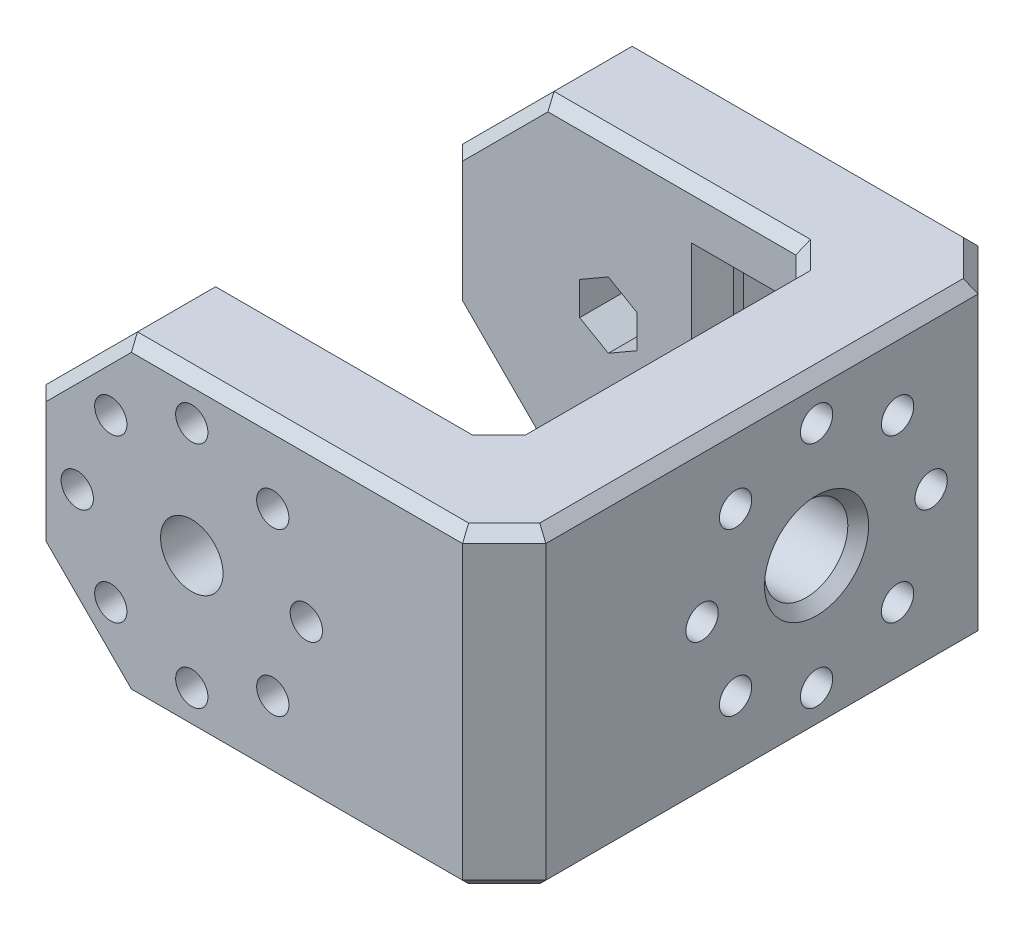
SolidWorks part; units mm, degrees
ref_plane "Alzado" through (0, 0, 0) normal (0, 0, 1) x (1, 0, 0)
ref_plane "Planta" through (0, 0, 0) normal (0, 1, 0) x (1, 0, 0)
ref_plane "Vista lateral" through (0, 0, 0) normal (1, 0, 0) x (0, 0, -1)
sketch "Croquis1" plane through (0, 0, 0) normal (0, 0, 1) x (1, 0, 0)
  line L0 (6.2132, 15) -> (30, 15)
  line L1 (15, -6.2132) -> (15, 6.2132) construction
  line L2 (15, 6.2132) -> (6.2132, 15) construction
  line L3 (6.2132, 15) -> (-6.2132, 15)
  line L4 (-6.2132, 15) -> (-15, 6.2132)
  line L5 (-15, 6.2132) -> (-15, -6.2132)
  line L6 (-15, -6.2132) -> (-6.2132, -15)
  line L7 (-6.2132, -15) -> (6.2132, -15)
  line L8 (6.2132, -15) -> (15, -6.2132) construction
  line L9 (30, 15) -> (30, -15)
  line L10 (30, -15) -> (6.2132, -15)
  circle A0 centre (0, 0) radius 15 construction
  dimension "D1" = 30
  dimension "D2" = 15
extrude "Saliente-Extruir1" add sketch "Croquis1" along normal blind 60
sketch "Croquis2" plane through (0, 15, 0) normal (0, 1, 0) x (1, 0, 0)
  line L0 (-15, -60) -> (-15, 0) construction
  line L1 (-15, -50.5) -> (20, -50.5)
  line L2 (-15, -50.5) -> (-15, -20)
  line L3 (-15, -20) -> (20, -20)
  line L4 (20, -50.5) -> (20, -20)
  line L5 (30, 0) -> (-6.2132, 0) construction
  line L6 (-15, -10.5) -> (20, -10.5)
  line L7 (-15, -10.5) -> (-15, 0)
  line L8 (-15, 0) -> (20, 0)
  line L9 (20, -10.5) -> (20, 0)
  line L10 (30, -60) -> (-6.2132, -60) construction
  line L11 (30, -60) -> (30, 0) construction
  dimension "D1" = 9.5
  dimension "D2" = 30.5
  dimension "D3" = 9.5
  dimension "D4" = 10
extrude "Cortar-Extruir1" cut sketch "Croquis2" against normal through all
sketch "Croquis3" plane through (0, 0, 60) normal (0, 0, 1) x (1, 0, 0)
  circle A0 centre (0, 0) radius 3
  dimension "D1" = 6
extrude "Cortar-Extruir2" cut sketch "Croquis3" against normal up to next
sketch "Croquis12" plane through (0, 0, 10.5) normal (0, 0, -1) x (-1, 0, 0)
  circle A0 centre (0, 0) radius 6
  dimension "D1" = 12
extrude "Saliente-Extruir2" add sketch "Croquis12" along normal blind 1
sketch "Croquis4" plane through (0, 0, 9.5) normal (0, 0, -1) x (-1, 0, 0)
  circle A0 centre (0, 0) radius 1.5
  dimension "D1" = 3
extrude "Cortar-Extruir3" cut sketch "Croquis4" against normal up to next
sketch "Croquis5" plane through (0, 0, 20) normal (0, 0, 1) x (1, 0, 0)
  line L1 (0, 3.1754) -> (-2.75, 1.5877)
  line L2 (-2.75, 1.5877) -> (-2.75, -1.5877)
  line L3 (-2.75, -1.5877) -> (0, -3.1754)
  line L4 (0, -3.1754) -> (2.75, -1.5877)
  line L5 (2.75, -1.5877) -> (2.75, 1.5877)
  line L6 (2.75, 1.5877) -> (0, 3.1754)
  circle A0 centre (0, 0) radius 2.75 construction
  dimension "D1" = 5.5
extrude "Cortar-Extruir4" cut sketch "Croquis5" against normal blind 5
sketch "Croquis9" plane through (0, 0, 20) normal (0, 0, 1) x (1, 0, 0)
  line L0 (20, -15) -> (20, 15) construction
  line L1 (20, -10) -> (10, -10)
  line L2 (20, -10) -> (20, 10)
  line L3 (20, 10) -> (10, 10)
  line L4 (10, -10) -> (10, 10)
  line L5 (-6.2132, -15) -> (30, -15) construction
  line L6 (30, 15) -> (-6.2132, 15) construction
  dimension "D1" = 5
  dimension "D2" = 5
  dimension "D3" = 10
extrude "Cortar-Extruir7" cut sketch "Croquis9" against normal blind 5
sketch "Croquis7" plane through (30, 0, 0) normal (1, 0, 0) x (0, 0, -1)
  line L0 (-60, 0) -> (0, 0) construction
  line L1 (-60, -15) -> (-60, 15) construction
  line L2 (-30, 15) -> (-30, -15) construction
  line L3 (-60, 15) -> (0, 15) construction
  line L4 (-60, -15) -> (0, -15) construction
  circle A0 centre (-30, 0) radius 4
  circle A1 centre (-30, 11) radius 1.55
  circle A2 centre (-22.2218, 7.7782) radius 1.55
  circle A3 centre (-19, 0) radius 1.55
  circle A4 centre (-22.2218, -7.7782) radius 1.55
  circle A5 centre (-30, -11) radius 1.55
  circle A6 centre (-37.7782, -7.7782) radius 1.55
  circle A7 centre (-41, 0) radius 1.55
  circle A8 centre (-37.7782, 7.7782) radius 1.55
  point P31 (-30, 0)
  dimension "D1" = 3.1
  dimension "D2" = 8
  dimension "D4" = 11
  dimension "D3" = 8
extrude "Cortar-Extruir5" cut sketch "Croquis7" against normal up to next
sketch "Croquis8" plane through (30, 0, 0) normal (1, 0, 0) x (0, 0, -1)
  line L0 (-19.9765, 5.5328) -> (-19.1546, 8.6)
  line L1 (-26.8246, 11) -> (-28.4123, 13.75)
  line L2 (-28.4123, 13.75) -> (-31.5877, 13.75)
  line L3 (-31.5877, 13.75) -> (-33.1754, 11)
  line L4 (-33.1754, 11) -> (-31.5877, 8.25)
  line L5 (-31.5877, 8.25) -> (-28.4123, 8.25)
  line L6 (-28.4123, 8.25) -> (-26.8246, 11)
  line L7 (-19.1546, 8.6) -> (-21.4, 10.8454)
  line L8 (-21.4, 10.8454) -> (-24.4672, 10.0235)
  line L9 (-24.4672, 10.0235) -> (-25.2891, 6.9563)
  line L10 (-25.2891, 6.9563) -> (-23.0437, 4.7109)
  line L11 (-23.0437, 4.7109) -> (-19.9765, 5.5328)
  line L12 (-19, -3.1754) -> (-16.25, -1.5877)
  line L13 (-16.25, -1.5877) -> (-16.25, 1.5877)
  line L14 (-16.25, 1.5877) -> (-19, 3.1754)
  line L15 (-19, 3.1754) -> (-21.75, 1.5877)
  line L16 (-21.75, 1.5877) -> (-21.75, -1.5877)
  line L17 (-21.75, -1.5877) -> (-19, -3.1754)
  line L18 (-24.4672, -10.0235) -> (-21.4, -10.8454)
  line L19 (-21.4, -10.8454) -> (-19.1546, -8.6)
  line L20 (-19.1546, -8.6) -> (-19.9765, -5.5328)
  line L21 (-19.9765, -5.5328) -> (-23.0437, -4.7109)
  line L22 (-23.0437, -4.7109) -> (-25.2891, -6.9563)
  line L23 (-25.2891, -6.9563) -> (-24.4672, -10.0235)
  line L24 (-33.1754, -11) -> (-31.5877, -13.75)
  line L25 (-31.5877, -13.75) -> (-28.4123, -13.75)
  line L26 (-28.4123, -13.75) -> (-26.8246, -11)
  line L27 (-26.8246, -11) -> (-28.4123, -8.25)
  line L28 (-28.4123, -8.25) -> (-31.5877, -8.25)
  line L29 (-31.5877, -8.25) -> (-33.1754, -11)
  line L30 (-40.0235, -5.5328) -> (-40.8454, -8.6)
  line L31 (-40.8454, -8.6) -> (-38.6, -10.8454)
  line L32 (-38.6, -10.8454) -> (-35.5328, -10.0235)
  line L33 (-35.5328, -10.0235) -> (-34.7109, -6.9563)
  line L34 (-34.7109, -6.9563) -> (-36.9563, -4.7109)
  line L35 (-36.9563, -4.7109) -> (-40.0235, -5.5328)
  line L36 (-41, 3.1754) -> (-43.75, 1.5877)
  line L37 (-43.75, 1.5877) -> (-43.75, -1.5877)
  line L38 (-43.75, -1.5877) -> (-41, -3.1754)
  line L39 (-41, -3.1754) -> (-38.25, -1.5877)
  line L40 (-38.25, -1.5877) -> (-38.25, 1.5877)
  line L41 (-38.25, 1.5877) -> (-41, 3.1754)
  line L42 (-35.5328, 10.0235) -> (-38.6, 10.8454)
  line L43 (-38.6, 10.8454) -> (-40.8454, 8.6)
  line L44 (-40.8454, 8.6) -> (-40.0235, 5.5328)
  line L45 (-40.0235, 5.5328) -> (-36.9563, 4.7109)
  line L46 (-36.9563, 4.7109) -> (-34.7109, 6.9563)
  line L47 (-34.7109, 6.9563) -> (-35.5328, 10.0235)
  circle A0 centre (-30, 11) radius 2.75 construction
  point P54 (-30, 0)
  dimension "D1" = 5.5
  dimension "D2" = 8
extrude "Cortar-Extruir6" cut sketch "Croquis8" against normal up to next from offset 5 offset against normal yes
sketch "Croquis10" plane through (0, 0, 60) normal (0, 0, 1) x (1, 0, 0)
  circle A0 centre (0, 11) radius 1.55
  circle A1 centre (0, 0) radius 3 construction
  circle A2 centre (7.7782, 7.7782) radius 1.55
  circle A3 centre (11, 0) radius 1.55
  circle A4 centre (7.7782, -7.7782) radius 1.55
  circle A5 centre (0, -11) radius 1.55
  circle A6 centre (-7.7782, -7.7782) radius 1.55
  circle A7 centre (-11, 0) radius 1.55
  circle A8 centre (-7.7782, 7.7782) radius 1.55
  point P21 (0, 0)
  dimension "D1" = 3.1
  dimension "D2" = 11
  dimension "D3" = 8
extrude "Cortar-Extruir8" cut sketch "Croquis10" against normal up to next
sketch "Croquis11" plane through (0, 0, 60) normal (0, 0, 1) x (1, 0, 0)
  line L0 (10.0235, 5.5328) -> (10.8454, 8.6)
  line L1 (3.1754, 11) -> (1.5877, 13.75)
  line L2 (1.5877, 13.75) -> (-1.5877, 13.75)
  line L3 (-1.5877, 13.75) -> (-3.1754, 11)
  line L4 (-3.1754, 11) -> (-1.5877, 8.25)
  line L5 (-1.5877, 8.25) -> (1.5877, 8.25)
  line L6 (1.5877, 8.25) -> (3.1754, 11)
  line L7 (10.8454, 8.6) -> (8.6, 10.8454)
  line L8 (8.6, 10.8454) -> (5.5328, 10.0235)
  line L9 (5.5328, 10.0235) -> (4.7109, 6.9563)
  line L10 (4.7109, 6.9563) -> (6.9563, 4.7109)
  line L11 (6.9563, 4.7109) -> (10.0235, 5.5328)
  line L12 (11, -3.1754) -> (13.75, -1.5877)
  line L13 (13.75, -1.5877) -> (13.75, 1.5877)
  line L14 (13.75, 1.5877) -> (11, 3.1754)
  line L15 (11, 3.1754) -> (8.25, 1.5877)
  line L16 (8.25, 1.5877) -> (8.25, -1.5877)
  line L17 (8.25, -1.5877) -> (11, -3.1754)
  line L18 (5.5328, -10.0235) -> (8.6, -10.8454)
  line L19 (8.6, -10.8454) -> (10.8454, -8.6)
  line L20 (10.8454, -8.6) -> (10.0235, -5.5328)
  line L21 (10.0235, -5.5328) -> (6.9563, -4.7109)
  line L22 (6.9563, -4.7109) -> (4.7109, -6.9563)
  line L23 (4.7109, -6.9563) -> (5.5328, -10.0235)
  line L24 (-3.1754, -11) -> (-1.5877, -13.75)
  line L25 (-1.5877, -13.75) -> (1.5877, -13.75)
  line L26 (1.5877, -13.75) -> (3.1754, -11)
  line L27 (3.1754, -11) -> (1.5877, -8.25)
  line L28 (1.5877, -8.25) -> (-1.5877, -8.25)
  line L29 (-1.5877, -8.25) -> (-3.1754, -11)
  line L30 (-10.0235, -5.5328) -> (-10.8454, -8.6)
  line L31 (-10.8454, -8.6) -> (-8.6, -10.8454)
  line L32 (-8.6, -10.8454) -> (-5.5328, -10.0235)
  line L33 (-5.5328, -10.0235) -> (-4.7109, -6.9563)
  line L34 (-4.7109, -6.9563) -> (-6.9563, -4.7109)
  line L35 (-6.9563, -4.7109) -> (-10.0235, -5.5328)
  line L36 (-11, 3.1754) -> (-13.75, 1.5877)
  line L37 (-13.75, 1.5877) -> (-13.75, -1.5877)
  line L38 (-13.75, -1.5877) -> (-11, -3.1754)
  line L39 (-11, -3.1754) -> (-8.25, -1.5877)
  line L40 (-8.25, -1.5877) -> (-8.25, 1.5877)
  line L41 (-8.25, 1.5877) -> (-11, 3.1754)
  line L42 (-5.5328, 10.0235) -> (-8.6, 10.8454)
  line L43 (-8.6, 10.8454) -> (-10.8454, 8.6)
  line L44 (-10.8454, 8.6) -> (-10.0235, 5.5328)
  line L45 (-10.0235, 5.5328) -> (-6.9563, 4.7109)
  line L46 (-6.9563, 4.7109) -> (-4.7109, 6.9563)
  line L47 (-4.7109, 6.9563) -> (-5.5328, 10.0235)
  circle A0 centre (0, 11) radius 2.75 construction
  circle A1 centre (7.7782, 7.7782) radius 2.75 construction
  circle A2 centre (11, 0) radius 2.75 construction
  circle A3 centre (7.7782, -7.7782) radius 2.75 construction
  circle A4 centre (0, -11) radius 2.75 construction
  circle A5 centre (-7.7782, -7.7782) radius 2.75 construction
  circle A6 centre (-11, 0) radius 2.75 construction
  circle A7 centre (-7.7782, 7.7782) radius 2.75 construction
  point P67 (0, 0)
  dimension "D1" = 5.5
  dimension "D2" = 8
extrude "Cortar-Extruir9" cut sketch "Croquis11" against normal up to next from offset 5 offset against normal yes
sketch "Croquis13" plane through (0, 15, 0) normal (0, 1, 0) x (1, 0, 0)
  line L1 (20, -10.5) -> (30, -10.5)
  line L2 (20, -10.5) -> (20, 0)
  line L3 (20, 0) -> (30, 0)
  line L4 (30, -10.5) -> (30, 0)
extrude "Cortar-Extruir10" cut sketch "Croquis13" against normal through all
chamfer "Chaflán7" distance 4 angle 45 2 edges at (30, 0, 10.5) (30, 0, 60)
chamfer "Chaflán5" distance 0.5 angle 45 1 edges at (-1.5, 0, 9.5)
chamfer "Chaflán6" distance 1 angle 45 1 edges at (6, 0, 10.5)
chamfer "Chaflán4" distance 1 angle 45 2 edges at (30, 4, 30) (20, 4, 30)
chamfer "Chaflán3" distance 1 angle 45 1 edges at (3, 0, 50.5)
chamfer "Chaflán1" distance 2 angle 45 6 edges at (20, 0, 50.5) (20, -12.5, 20) (20, 12.5, 20) (20, 0, 15) (10, 0, 20) (10, 0, 15)
chamfer "Chaflán2" distance 1 angle 45 32 edges at (19, -15, 21) (20, -15, 35.25) (19, -15, 49.5) (5.8934, -15, 50.5) (-10.6066, -10.6066, 50.5) (5.8934, -15, 20) (-10.6066, -10.6066, 20) (-15, 0, 20) (-10.6066, 10.6066, 20) (5.8934, 15, 20) (-15, 0, 50.5) (-10.6066, 10.6066, 50.5) (20, 15, 35.25) (5.8934, 15, 50.5) (19, 15, 49.5) (-10.6066, 10.6066, 60) (-15, 0, 60) (-10.6066, -10.6066, 60) (9.8934, -15, 60) (30, -15, 35.25) (-15, 0, 10.5) (-10.6066, -10.6066, 10.5) (9.8934, -15, 10.5) (-10.6066, 10.6066, 10.5) (9.8934, 15, 10.5) (9.8934, 15, 60) (30, 15, 35.25) (19, 15, 21) (28, 15, 12.5) (28, -15, 12.5) (28, -15, 58) (28, 15, 58)
